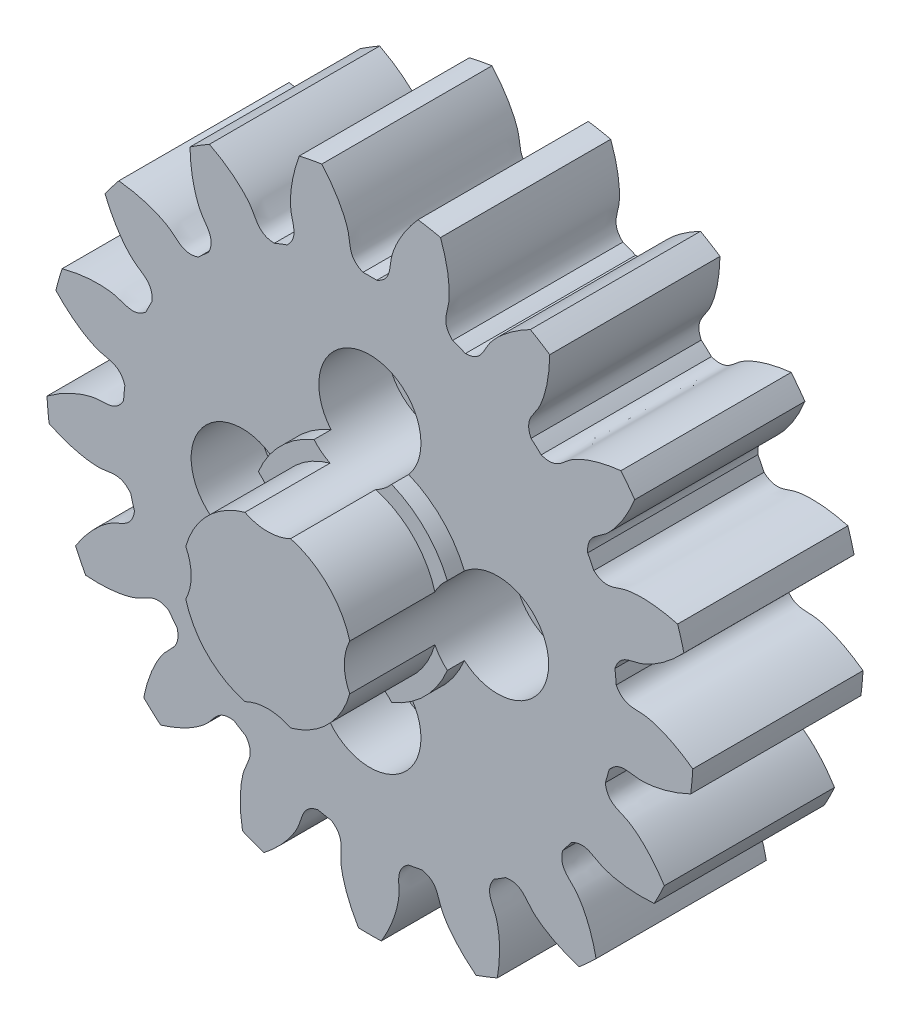
SolidWorks part; units mm, degrees
ref_plane "前视基准面" through (0, 0, 0) normal (0, 0, 1) x (1, 0, 0)
ref_plane "上视基准面" through (0, 0, 0) normal (0, 1, 0) x (1, 0, 0)
ref_plane "右视基准面" through (0, 0, 0) normal (1, 0, 0) x (0, 0, -1)
sketch "草图1" plane through (0, 0, 0) normal (0, 0, 1) x (1, 0, 0)
  circle A0 centre (0, 0) radius 19
extrude "凸台-拉伸1" add sketch "草图1" along normal blind 10
ref_axis "基准轴1" through (0, 0, -0.5) along (0, 0, 1)
sketch "草图2" plane through (0, 0, 0) normal (0, 0, 1) x (1, 0, 0)
  line L0 (0, 0) -> (0, 19) construction
  circle A0 centre (0, 0) radius 19 construction
  arc A1 (0.4034, 14.4944) -> (-0.4034, 14.4944) centre (0, 0) ccw
  arc A2 (6.2313, 21.4814) -> (-6.2313, 21.4814) centre (0, 0) ccw
  arc A3 (-6.2313, 21.4814) -> (6.2313, 21.4814) centre (0, 0) ccw construction
  spline S0 degree 3 poles (0.4034, 14.4944) (1.2558, 14.8496) (1.1324, 15.5096) (1.2766, 16.1296) (1.29, 16.1823) (1.306, 16.2408) (1.3251, 16.3052) (1.3474, 16.3752) (1.3731, 16.4508) (1.4025, 16.5319) (1.4359, 16.6184) (1.4733, 16.7101) (1.5152, 16.8068) (1.5616, 16.9086) (1.6128, 17.0151) (1.669, 17.1264) (1.7304, 17.2421) (1.7972, 17.3621) (1.8696, 17.4863) (1.9478, 17.6145) (2.032, 17.7465) (2.1224, 17.8821) (2.2191, 18.0211) (2.3223, 18.1634) (2.4322, 18.3086) (2.5489, 18.4566) (2.6727, 18.6072) (2.8035, 18.7601) (2.9417, 18.9152) (3.0873, 19.0722) (3.2404, 19.2308) (3.4012, 19.3908) (3.5698, 19.552) (3.7462, 19.7141) (3.9307, 19.8769) (4.1233, 20.0401) (4.324, 20.2035) (4.533, 20.3667) (4.7503, 20.5295) (4.9761, 20.6917) (5.2103, 20.853) (5.453, 21.0131) (5.7916, 21.2269) (6.0532, 21.3811) (6.2313, 21.4814) knots 0 0 0 0 0.193883 0.199024 0.204851 0.211363 0.21856 0.226443 0.235011 0.244265 0.254205 0.264829 0.27614 0.288136 0.300817 0.314184 0.328236 0.342973 0.358397 0.374505 0.391299 0.408779 0.426944 0.445795 0.465331 0.485552 0.506459 0.528051 0.550329 0.573293 0.596941 0.621276 0.646296 0.672001 0.698392 0.725468 0.753229 0.781677 0.810809 0.840627 0.871131 0.90232 0.934195 1 1 1 1
  spline S1 degree 3 poles (-0.4034, 14.4944) (-1.2558, 14.8496) (-1.1324, 15.5096) (-1.2766, 16.1296) (-1.29, 16.1823) (-1.306, 16.2408) (-1.3251, 16.3052) (-1.3474, 16.3752) (-1.3731, 16.4508) (-1.4025, 16.5319) (-1.4359, 16.6184) (-1.4733, 16.7101) (-1.5152, 16.8068) (-1.5616, 16.9086) (-1.6128, 17.0151) (-1.669, 17.1264) (-1.7304, 17.2421) (-1.7972, 17.3621) (-1.8696, 17.4863) (-1.9478, 17.6145) (-2.032, 17.7465) (-2.1224, 17.8821) (-2.2191, 18.0211) (-2.3223, 18.1634) (-2.4322, 18.3086) (-2.5489, 18.4566) (-2.6727, 18.6072) (-2.8035, 18.7601) (-2.9417, 18.9152) (-3.0873, 19.0722) (-3.2404, 19.2308) (-3.4012, 19.3908) (-3.5698, 19.552) (-3.7462, 19.7141) (-3.9307, 19.8769) (-4.1233, 20.0401) (-4.324, 20.2035) (-4.533, 20.3667) (-4.7503, 20.5295) (-4.9761, 20.6917) (-5.2103, 20.853) (-5.453, 21.0131) (-5.7916, 21.2269) (-6.0532, 21.3811) (-6.2313, 21.4814) knots 0 0 0 0 0.193883 0.199024 0.204851 0.211363 0.21856 0.226443 0.235011 0.244265 0.254205 0.264829 0.27614 0.288136 0.300817 0.314184 0.328236 0.342973 0.358397 0.374505 0.391299 0.408779 0.426944 0.445795 0.465331 0.485552 0.506459 0.528051 0.550329 0.573293 0.596941 0.621276 0.646296 0.672001 0.698392 0.725468 0.753229 0.781677 0.810809 0.840627 0.871131 0.90232 0.934195 1 1 1 1
extrude "切除-拉伸1" cut sketch "草图2" along normal through all
pattern_circular "阵列(圆周)1" count 17 every 21.176 about axis through (0, 0, -0.5) along (0, 0, 1) of "切除-拉伸1"
sketch "草图3" plane through (0, 0, 0) normal (0, 0, 1) x (1, 0, 0)
  circle A0 centre (0, 0) radius 17 construction
  dimension "Dn" = 34
sketch "草图4" plane through (0, 0, 10) normal (0, 0, 1) x (1, 0, 0)
  circle A0 centre (0, 0) radius 6
  dimension "D1" = 12
extrude "凸台-拉伸2" add sketch "草图4" along normal blind 1
sketch "草图5" plane through (0, 0, 11) normal (0, 0, 1) x (1, 0, 0)
  circle A0 centre (0, 0) radius 5
  dimension "D1" = 10
extrude "凸台-拉伸3" add sketch "草图5" along normal blind 5
sketch "草图6" plane through (0, 0, 10) normal (0, 0, 1) x (1, 0, 0)
  circle A0 centre (0, 0) radius 7.5 construction
  circle A1 centre (0, 7.5) radius 1.25
  circle A2 centre (7.5, 0) radius 1.25
  circle A3 centre (0, -7.5) radius 1.25
  circle A4 centre (-7.5, 0) radius 1.25
  dimension "D1" = 15
  dimension "D2" = 2.5
extrude "切除-拉伸2" cut sketch "草图6" against normal up to next
sketch "草图7" plane through (0, 0, 0) normal (0, 0, -1) x (-1, 0, 0)
  circle A0 centre (0, 0) radius 2.5
  dimension "D1" = 5
extrude "切除-拉伸3" cut sketch "草图7" against normal blind 5
sketch "草图8" plane through (0, 0, 16) normal (0, 0, 1) x (1, 0, 0)
  circle A0 centre (0, 7.5) radius 3
  circle A1 centre (7.5, 0) radius 3
  circle A2 centre (0, -7.5) radius 3
  circle A3 centre (-7.5, 0) radius 3
  point P3 (-7.5, 0)
  point P12 (0, 0)
  dimension "D1" = 6
  dimension "D2" = 4
extrude "切除-拉伸4" cut sketch "草图8" against normal blind 10
